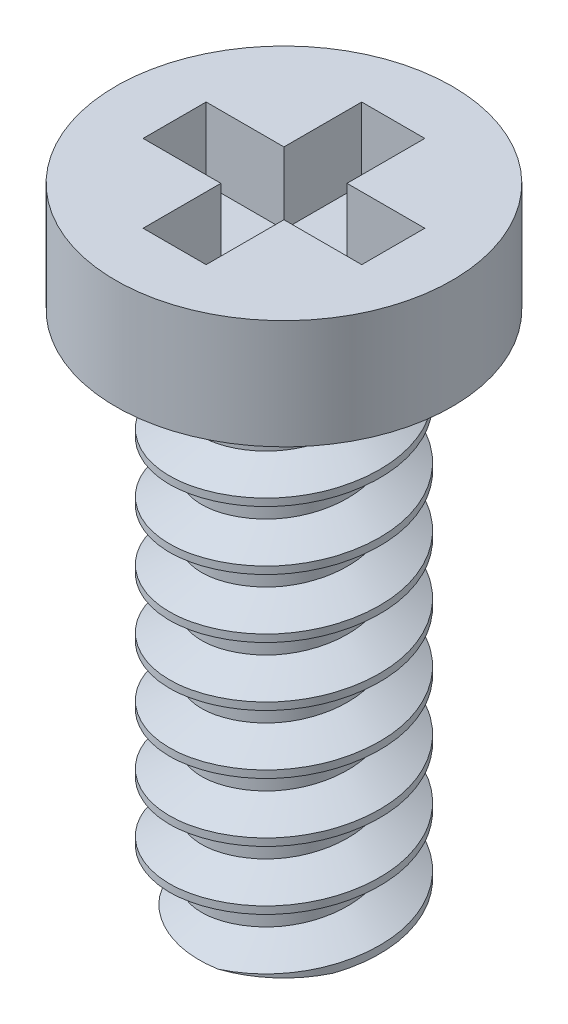
SolidWorks part; units mm, degrees
ref_plane "Front Plane" through (0, 0, 0) normal (0, 0, 1) x (1, 0, 0)
ref_plane "Top Plane" through (0, 0, 0) normal (0, 1, 0) x (1, 0, 0)
ref_plane "Right Plane" through (0, 0, 0) normal (1, 0, 0) x (0, 0, -1)
sketch "Sketch1" plane through (0, 0, 0) normal (1, 0, 0) x (0, 0, -1)
  line L0 (0, 0) -> (0, 7.3) construction
  line L1 (0, 7.3) -> (2, 7.3)
  line L2 (2, 7.3) -> (2, 6)
  line L3 (2, 6) -> (1.25, 6)
  line L4 (1.25, 6) -> (1.25, 0)
  line L5 (1.25, 0) -> (0, 0)
  line L6 (0, 0) -> (0, 7.3)
  dimension "D1" = 7.3
  dimension "D2" = 4
  dimension "D3" = 1.3
  dimension "D4" = 2.5
revolve "Revolve1" add sketch "Sketch1" angle 360 about L0
thread "Thread1" pitch 0.7 method cut profile "Thread Profile1" start angle 0, offset 0, length 10, pitch 0.7, diameter 2.5
ref_plane "Plane1" through (-1.25, 6, 0) normal (0, 0, 1) x (-1, 0, 0)
sketch "Thread Profile1" plane through (-1.25, 6, 0) normal (0, 0, 1) x (-1, 0, 0)
  line L0 (0, 0) -> (0, 0.7) construction
  line L11 (0, 0) -> (0, 0.6125)
  line L12 (0, 0.6125) -> (-0.3789, 0.3937)
  line L13 (-0.3789, 0.3937) -> (-0.3789, 0.2187)
  line L15 (-0.3789, 0.2187) -> (0, 0)
  line L17 (-0.3789, 0.3062) -> (0, 0.3062) construction
  point P2 (0, 0)
  dimension "Pitch" = 0.7
  dimension "Profile_Angle" = 60
  dimension "Profile_Land" = 0.175
  dimension "Profile_Height" = 0.3789
sketch "Sketch4" plane through (0, 7.3, 0) normal (0, 1, 0) x (1, 0, 0)
  line L0 (0.375, -0.375) -> (0.375, -1.3)
  line L1 (0.375, 0.375) -> (-0.375, -0.375) construction
  line L2 (-0.375, 1.3) -> (-0.375, 0.375)
  line L3 (1.3, 0.375) -> (0.375, 0.375)
  line L4 (0.375, 1.3) -> (0.375, 0.375)
  line L5 (1.3, -0.375) -> (0.375, -0.375)
  line L6 (0.375, -1.3) -> (-0.375, -1.3)
  line L7 (-1.3, -0.375) -> (-1.3, 0.375)
  line L8 (1.3, -0.375) -> (1.3, 0.375)
  line L9 (0.375, 1.3) -> (-0.375, 1.3)
  line L10 (-0.375, 0.375) -> (0.375, -0.375) construction
  line L11 (-0.375, -0.375) -> (-1.3, -0.375)
  line L12 (1.3, 0) -> (-1.3, 0) construction
  line L13 (0, -1.3) -> (0, 1.3) construction
  line L14 (-0.375, -0.375) -> (-0.375, -1.3)
  line L16 (-0.375, 0.375) -> (-1.3, 0.375)
  point P2 (0, 0)
  point P3 (-0.2, -1.7157)
  point P4 (0, 0)
  point P5 (0, 0)
  point P7 (0, 0)
  point P22 (0, 0)
  dimension "D3" = 2.6
  dimension "D1" = 2.6
  dimension "D2" = 0.75
extrude "Cut-Extrude1" cut sketch "Sketch4" against normal blind 0.85
